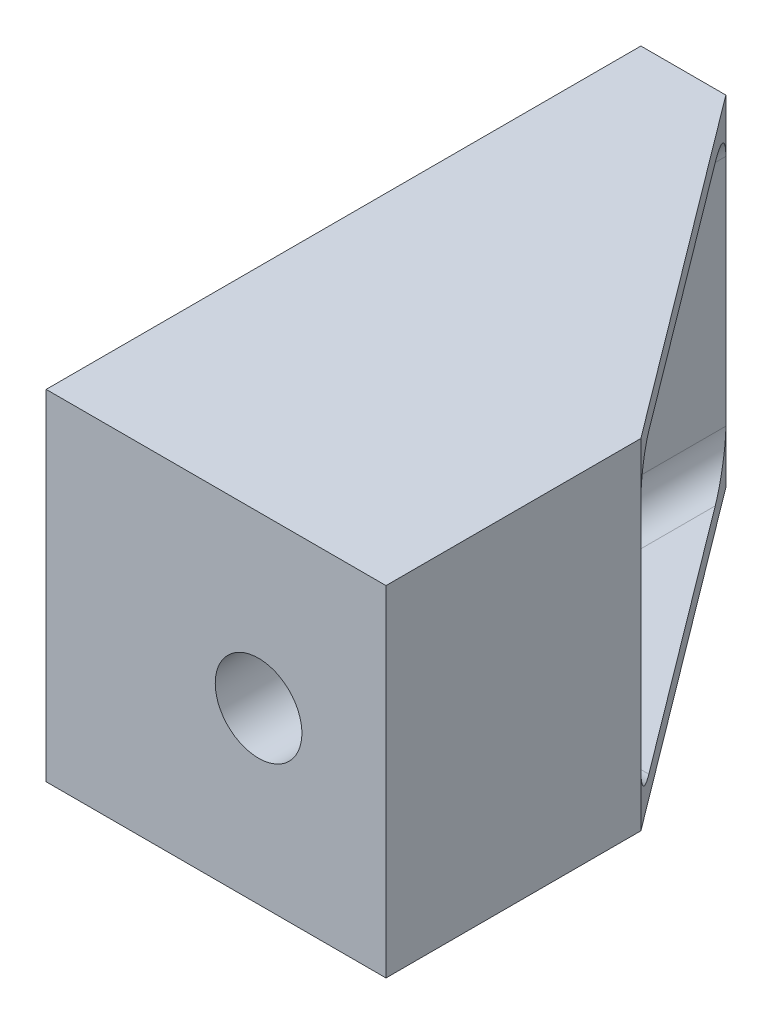
SolidWorks part; units mm, degrees
ref_plane "Front Plane" through (0, 0, 0) normal (0, 0, 1) x (1, 0, 0)
ref_plane "Top Plane" through (0, 0, 0) normal (0, 1, 0) x (1, 0, 0)
ref_plane "Right Plane" through (0, 0, 0) normal (1, 0, 0) x (0, 0, -1)
sketch "Sketch2" plane through (0, 0, 0) normal (1, 0, 0) x (0, 0, -1)
  line L0 (0, 0) -> (25.4, 0) construction
  line L1 (0, 25.4) -> (50.8, 25.4)
  line L2 (0, 25.4) -> (0, -25.4)
  line L3 (0, -25.4) -> (50.8, -25.4)
  line L4 (32.7323, -12.7) -> (32.7323, 12.7) construction
  line L5 (32.7323, 12.7) -> (10.7353, 0) construction
  line L6 (10.7353, 0) -> (32.7323, -12.7) construction
  line L7 (32.7323, -12.7) -> (21.7338, 6.35) construction
  line L8 (32.7323, 12.7) -> (21.7338, -6.35) construction
  line L9 (10.7353, 0) -> (32.7323, 0) construction
  line L10 (50.8, -25.4) -> (50.8, 25.4)
  circle A0 centre (25.4, 0) radius 7.62
  circle A2 centre (32.7323, 12.7) radius 2.4765
  circle A3 centre (32.7323, -12.7) radius 2.4765
  circle A4 centre (10.7353, 0) radius 2.4765
  point P0 (0, 0)
  point P9 (25.4, 0)
  dimension "D2" = 15.24
  dimension "D3" = 25.4
  dimension "D4" = 25.4
  dimension "D5" = 4.953
  dimension "D1" = 50.8
  dimension "D6" = 50.8
extrude "Boss-Extrude1" add sketch "Sketch2" along normal blind 6.35
sketch "Sketch3" plane through (0, 0, 0) normal (0, 0, 1) x (1, 0, 0)
  line L0 (44.45, 0) -> (0, 0) construction
  line L1 (0, 25.4) -> (44.45, 25.4)
  line L2 (0, 25.4) -> (0, -25.4)
  line L3 (0, -25.4) -> (44.45, -25.4)
  line L4 (44.45, 25.4) -> (44.45, -25.4)
  circle A0 centre (25.4, 0) radius 6.35
  dimension "D2" = 12.7
  dimension "D1" = 44.45
  dimension "D3" = 19.05
extrude "Boss-Extrude2" add sketch "Sketch3" along normal blind 12.7
sketch "Sketch5" plane through (0, 0, 12.7) normal (0, 0, 1) x (1, 0, 0)
  circle A0 centre (25.4, 0) radius 6.35
  circle A1 centre (25.4, 0) radius 12.065
  dimension "D1" = 12.7
  dimension "D2" = 24.13
sketch "Sketch9" plane through (0, 0, 0) normal (0, 0, -1) x (-1, 0, 0)
  circle A0 centre (-25.4, 0) radius 12.7
  dimension "D1" = 25.4
extrude "Cut-Extrude2" cut sketch "Sketch9" against normal blind 10.16
sketch "Sketch13" plane through (0, 25.4, 0) normal (0, 1, 0) x (1, 0, 0)
  line L3 (44.45, 0) -> (6.35, 50.8)
rib "Rib8" sketch "Sketch13" sketch "Sketch13" thickness 3.175 extrusion direction parallel to sketch draft on no parameters "D1"=3.175
sketch "Sketch14" plane through (0, -25.4, 0) normal (0, -1, 0) x (-1, 0, 0)
  line L0 (-44.45, 0) -> (-6.35, 50.8)
rib "Rib9" sketch "Sketch14" sketch "Sketch14" thickness 3.175 extrusion direction parallel to sketch draft on no parameters "D1"=3.175
fillet "Fillet1" [suppressed] radius 3.175
sketch3d "3DSketch1"
  line L0 (6.35, -22.225, 0) -> (6.35, -22.225, -50.8) construction
  line L1 (6.35, 22.225, 0) -> (6.35, -22.225, 0) construction
  line L2 (6.35, -22.225, 0) -> (44.45, -22.225, 0) construction
  line L3 (6.35, -22.225, 0) -> (25.4, -22.225, 0) construction
  line L4 (6.35, -3.175, 0) -> (6.35, -22.225, 0) construction
  line L5 (6.35, -22.225, 0) -> (6.35, -22.225, -19.05) construction
  point P0 (6.35, -22.225, 0)
  point P1 (6.35, -22.225, -19.05)
  point P3 (6.35, -3.175, 0)
  point P6 (25.4, -22.225, 0)
  dimension "D1" = 19.05
ref_plane "Plane2" through (1.0583, 1.0583, -1.0583) normal (-0.5774, -0.5774, 0.5774) x (0.8165, -0.4082, 0.4082)
sketch "Sketch17" plane through (1.0583, 1.0583, -1.0583) normal (-0.5774, -0.5774, 0.5774) x (0.8165, -0.4082, 0.4082)
  line L0 (6.4809, -29.1858) -> (6.4809, -2.2451)
  line L1 (6.4809, -2.2451) -> (29.8123, -15.7154)
  line L2 (29.8123, -15.7154) -> (6.4809, -29.1858)
extrude "Boss-Extrude5" add sketch "Sketch17" along normal up to body separate body
mirror "Mirror1" about plane through (0, 0, 0) normal (0, 1, 0) of "Boss-Extrude5"
fillet "Fillet2" radius 4.7625 11 edges at (34.925, 22.225, 0) (6.35, 22.225, -34.925) (6.35, -22.225, -34.925) (34.925, -22.225, 0) (6.35, 0, 0) (15.875, 22.225, -9.525) (15.875, 12.7, 0) (6.35, 12.7, -9.525) (6.35, -12.7, -9.525) (15.875, -22.225, -9.525) (15.875, -12.7, 0)
sketch "Sketch20" plane through (0, 0, 12.7) normal (0, 0, 1) x (1, 0, 0)
  line L1 (44.45, 25.4) -> (0, 25.4)
  line L2 (44.45, 25.4) -> (44.45, -25.4)
  line L3 (44.45, -25.4) -> (0, -25.4)
  line L4 (0, 25.4) -> (0, -25.4)
  circle A0 centre (25.4, 0) radius 6.477
sketch "Sketch21" plane through (0, 0, 12.7) normal (0, 0, 1) x (1, 0, 0)
sketch "Sketch22" plane through (0, 0, 12.7) normal (0, 0, 1) x (1, 0, 0)
  line L1 (44.45, -25.4) -> (0, -25.4)
  line L2 (44.45, -25.4) -> (44.45, 25.4)
  line L3 (44.45, 25.4) -> (0, 25.4)
  line L4 (0, -25.4) -> (0, 25.4)
  circle A0 centre (25.4, 0) radius 11.1842
extrude "Boss-Extrude6" add sketch "Sketch22" along normal blind 25.4 contours L2 L1 L4 L3
extrude "Cut-Extrude3" cut sketch "Sketch20" along normal blind 50.8 contours A0
sketch "Sketch23" plane through (6.35, 0, 0) normal (1, 0, 0) x (0, 0, -1)
  circle A0 centre (25.4, 0) radius 19.177
  dimension "D1" = 38.354
extrude "Cut-Extrude4" cut sketch "Sketch23" along normal blind 15.494
sketch "Sketch25" plane through (0, 0, 0) normal (-1, 0, 0) x (0, 0, 1)
  line L4 (-50.8, -25.4) -> (38.1, -25.4)
  line L5 (38.1, -25.4) -> (38.1, 25.4)
  line L6 (38.1, 25.4) -> (-50.8, 25.4)
  line L7 (-50.8, 25.4) -> (-50.8, -25.4)
  line L8 (-50.8, -25.4) -> (38.1, -25.4)
  line L9 (38.1, -25.4) -> (38.1, 25.4)
  line L10 (38.1, 25.4) -> (-50.8, 25.4)
  line L11 (-50.8, 25.4) -> (-50.8, -25.4)
  circle A1 centre (-32.7323, -12.7) radius 2.4765
  circle A2 centre (-32.7323, -12.7) radius 2.4765
  circle A3 centre (-10.7353, 0) radius 2.4765
  circle A4 centre (-10.7353, 0) radius 2.4765
  circle A5 centre (-32.7323, 12.7) radius 2.4765
  circle A6 centre (-32.7323, 12.7) radius 2.4765
  circle A7 centre (-25.4, 0) radius 7.62
  circle A8 centre (-25.4, 0) radius 7.62
  dimension "D1" = 0
  dimension "D2" = 0
  dimension "D3" = 0
  dimension "D4" = 0
  dimension "D5" = 0
extrude "Boss-Extrude7" add sketch "Sketch25" along normal blind 6.35
